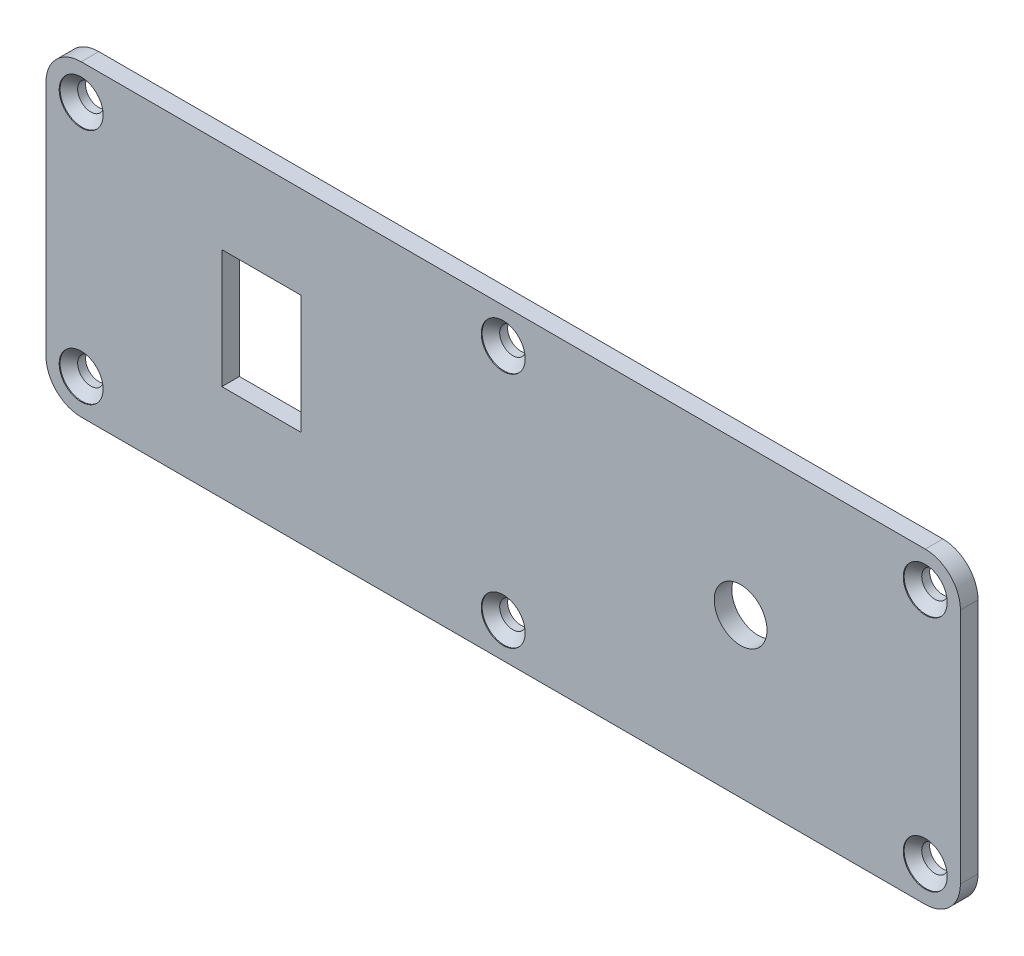
SolidWorks part; units mm, degrees
ref_plane "Ön Düzlem" through (0, 0, 0) normal (0, 0, 1) x (1, 0, 0)
ref_plane "Üst Düzlem" through (0, 0, 0) normal (0, 1, 0) x (1, 0, 0)
ref_plane "Sağ Düzlem" through (0, 0, 0) normal (1, 0, 0) x (0, 0, -1)
sketch "Çizim1" plane through (0, 0, 0) normal (0, 0, 1) x (1, 0, 0)
  line L1 (0, 0) -> (-104, 0)
  line L2 (0, 0) -> (0, 35)
  line L3 (0, 35) -> (-104, 35)
  line L4 (-104, 0) -> (-104, 35)
  dimension "D1" = 104
  dimension "D2" = 35
extrude "Yükseklik-Ekstrüzyon1" add sketch "Çizim1" along normal blind 2
sketch "Çizim2" plane through (0, 0, 2) normal (0, 0, 1) x (1, 0, 0)
  line L0 (0, 35) -> (-104, 35) construction
  line L1 (-104, 35) -> (-104, 0) construction
  line L2 (-104, 0) -> (0, 0) construction
  line L3 (-52, 35) -> (-52, 0) construction
  circle A0 centre (-100, 31) radius 1.5
  circle A1 centre (-100, 4) radius 1.5
  circle A2 centre (-4, 4) radius 1.5
  circle A3 centre (-4, 31) radius 1.5
  dimension "D1" = 3
  dimension "D2" = 3
  dimension "D3" = 4
  dimension "D4" = 4
  dimension "D5" = 27
  dimension "D6" = 4
  dimension "D7" = 4
extrude "Kes-Ekstrüzyon1" cut sketch "Çizim2" against normal blind 2
sketch "Çizim3" plane through (0, 0, 2) normal (0, 0, 1) x (1, 0, 0)
  line L0 (-52, 35) -> (-52, 0) construction
  line L1 (0, 35) -> (-104, 35) construction
  line L2 (-104, 0) -> (0, 0) construction
  circle A0 centre (-100, 31) radius 2.5
  circle A1 centre (-100, 4) radius 2.5
  circle A2 centre (-4, 4) radius 2.5
  circle A3 centre (-4, 31) radius 2.5
  dimension "D1" = 5
  dimension "D2" = 5
extrude "Kes-Ekstrüzyon2" cut sketch "Çizim3" against normal blind 0.1
chamfer "Pah2" distance 1 angle 45 4 edges at (-5.5, 4, 1.9) (-5.5, 31, 1.9) (-98.5, 4, 1.9) (-98.5, 31, 1.9)
sketch "Çizim4" plane through (0, 0, 2) normal (0, 0, 1) x (1, 0, 0)
  line L0 (0, 35) -> (-104, 35) construction
  line L2 (-104, 35) -> (-104, 0) construction
  circle A0 centre (-52, 31) radius 1.5
  circle A1 centre (-52, 4) radius 1.5
  point P4 (0, 0)
  dimension "D1" = 3
  dimension "D2" = 3
  dimension "D3" = 27
  dimension "D4" = 4
  dimension "D5" = 52
  dimension "D6" = 52
extrude "Kes-Ekstrüzyon3" cut sketch "Çizim4" against normal blind 2
sketch "Çizim5" plane through (0, 0, 2) normal (0, 0, 1) x (1, 0, 0)
  circle A0 centre (-52, 31) radius 2.5
  circle A1 centre (-52, 4) radius 2.5
  dimension "D1" = 5
  dimension "D2" = 5
extrude "Kes-Ekstrüzyon4" cut sketch "Çizim5" against normal blind 0.1
chamfer "Pah3" distance 1 angle 45 2 edges at (-50.5, 4, 1.9) (-50.5, 31, 1.9)
fillet "Radyus1" radius 4 4 edges at (0, 0, 1) (0, 35, 1) (-104, 0, 1) (-104, 35, 1)
sketch "Çizim7" plane through (0, 0, 2) normal (0, 0, 1) x (1, 0, 0)
  line L0 (-4, 35) -> (-100, 35) construction
  line L1 (-84, 24.5) -> (-75, 24.5)
  line L2 (-84, 24.5) -> (-84, 11)
  line L3 (-84, 11) -> (-75, 11)
  line L4 (-75, 24.5) -> (-75, 11)
  line L5 (-104, 31) -> (-104, 4) construction
  line L6 (0, 4) -> (0, 31) construction
  circle A0 centre (-25, 18) radius 3
  dimension "D5" = 6
  dimension "D7" = 17
  dimension "D1" = 9
  dimension "D2" = 13.5
  dimension "D3" = 10.5
  dimension "D4" = 20
  dimension "D6" = 25
extrude "Kes-Ekstrüzyon6" cut sketch "Çizim7" against normal blind 2
